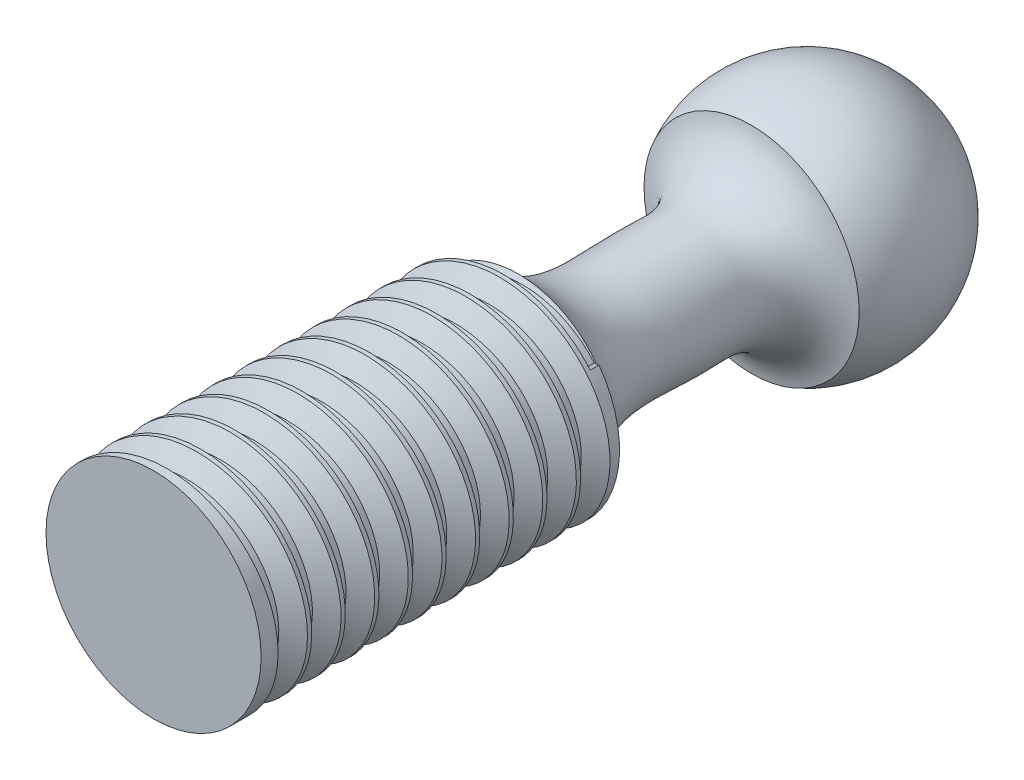
SolidWorks part; units mm, degrees
material "AISI 316L"
ref_plane "Piano frontale" through (0, 0, 0) normal (0, 0, 1) x (1, 0, 0)
ref_plane "Piano superiore" through (0, 0, 0) normal (0, 1, 0) x (1, 0, 0)
ref_plane "Piano destro" through (0, 0, 0) normal (1, 0, 0) x (0, 0, -1)
sketch "Schizzo2" plane through (0, 0, 0) normal (0, 0, 1) x (1, 0, 0)
  line L0 (13.398, -1.3546) -> (22.398, -1.3546)
  arc A0 (22.398, -1.3546) -> (13.398, -1.3546) centre (17.898, -1.3546) ccw
  dimension "D1" = 9
revolve "Rivoluzione1" add sketch "Schizzo2" angle 360 about L0
sketch "Schizzo3" plane through (0, 0, 0) normal (0, 0, 1) x (1, 0, 0)
  circle A0 centre (17.898, -1.3546) radius 4
  dimension "D1" = 8
extrude "Estrusione-Estrusione1" add sketch "Schizzo3" along normal blind 24.3
thread "Filettatura1" pitch 1.25 method cut profile "Profilo filettatura1" start angle 360, offset 0, length 13, pitch 1.25, diameter 8
ref_plane "Piano1" through (13.898, -1.3546, 24.3) normal (0, -1, 0) x (-1, 0, 0)
sketch "Profilo filettatura1" plane through (13.898, -1.3546, 24.3) normal (0, -1, 0) x (-1, 0, 0)
  line L0 (0, 0) -> (0, 1.25) construction
  line L11 (0, 0) -> (0, 1.0937)
  line L12 (0, 1.0937) -> (-0.6766, 0.7031)
  line L13 (-0.6766, 0.7031) -> (-0.6766, 0.3906)
  line L15 (-0.6766, 0.3906) -> (0, 0)
  line L17 (-0.6766, 0.5469) -> (0, 0.5469) construction
  point P2 (0, 0)
  dimension "Pitch" = 1.25
  dimension "Profile_Angle" = 60
  dimension "Profile_Land" = 0.3125
  dimension "Profile_Height" = 0.6766
sketch "Schizzo4" plane through (0, 0, 0) normal (0, 1, 0) x (1, 0, 0)
  line L0 (13.898, -2.0616) -> (21.898, -2.0616) construction
  line L1 (21.898, -11.3313) -> (21.898, -2.0616) construction
  line L2 (21.898, -2.0616) -> (21.898, -10.1117)
  line L3 (17.898, -2.0616) -> (17.898, -10.3938) construction
  arc A0 (21.898, -2.0616) -> (21.898, -10.1117) centre (26.3476, -6.0866) ccw
  spline S0 degree 2 poles (13.898, -23.2063) (13.898, -23.1281) (15.0696, -23.05) (16.2411, -22.9719) (17.898, -22.8937) (19.5549, -22.8156) (20.7264, -22.7375) (21.898, -22.6594) (21.898, -22.5812) (21.898, -22.5031) (20.7264, -22.425) (19.5549, -22.3469) (17.898, -22.2687) (16.2411, -22.1906) (15.0696, -22.1125) (13.898, -22.0344) (13.898, -21.9563) (13.898, -21.8781) (15.0696, -21.8) (16.2411, -21.7219) (17.898, -21.6437) (19.5549, -21.5656) (20.7264, -21.4875) (21.898, -21.4094) (21.898, -21.3312) (21.898, -21.2531) (20.7264, -21.175) (19.5549, -21.0969) (17.898, -21.0187) (16.2411, -20.9406) (15.0696, -20.8625) (13.898, -20.7844) (13.898, -20.7063) (13.898, -20.6281) (15.0696, -20.55) (16.2411, -20.4719) (17.898, -20.3937) (19.5549, -20.3156) (20.7264, -20.2375) (21.898, -20.1594) (21.898, -20.0812) (21.898, -20.0031) (20.7264, -19.925) (19.5549, -19.8469) (17.898, -19.7687) (16.2411, -19.6906) (15.0696, -19.6125) (13.898, -19.5344) (13.898, -19.4563) (13.898, -19.3781) (15.0696, -19.3) (16.2411, -19.2219) (17.898, -19.1437) (19.5549, -19.0656) (20.7264, -18.9875) (21.898, -18.9094) (21.898, -18.8312) (21.898, -18.7531) (20.7264, -18.675) (19.5549, -18.5969) (17.898, -18.5187) (16.2411, -18.4406) (15.0696, -18.3625) (13.898, -18.2844) (13.898, -18.2063) (13.898, -18.1281) (15.0696, -18.05) (16.2411, -17.9719) (17.898, -17.8937) (19.5549, -17.8156) (20.7264, -17.7375) (21.898, -17.6594) (21.898, -17.5812) (21.898, -17.5031) (20.7264, -17.425) (19.5549, -17.3469) (17.898, -17.2688) (16.2411, -17.1906) (15.0696, -17.1125) (13.898, -17.0344) (13.898, -16.9563) (13.898, -16.8781) (15.0696, -16.8) (16.2411, -16.7219) (17.898, -16.6438) (19.5549, -16.5656) (20.7264, -16.4875) (21.898, -16.4094) (21.898, -16.3312) (21.898, -16.2531) (20.7264, -16.175) (19.5549, -16.0969) (17.898, -16.0188) (16.2411, -15.9406) (15.0696, -15.8625) (13.898, -15.7844) (13.898, -15.7063) (13.898, -15.6281) (15.0696, -15.55) (16.2411, -15.4719) (17.898, -15.3938) (19.5549, -15.3156) (20.7264, -15.2375) (21.898, -15.1594) (21.898, -15.0812) (21.898, -15.0031) (20.7264, -14.925) (19.5549, -14.8469) (17.898, -14.7688) (16.2411, -14.6906) (15.0696, -14.6125) (13.898, -14.5344) (13.898, -14.4563) (13.898, -14.3781) (15.0696, -14.3) (16.2411, -14.2219) (17.898, -14.1438) (19.5548, -14.0656) (20.7264, -13.9875) (21.898, -13.9094) (21.898, -13.8312) (21.898, -13.7531) (20.7264, -13.675) (19.5548, -13.5969) (17.898, -13.5188) (16.2411, -13.4406) (15.0696, -13.3625) (13.898, -13.2844) (13.898, -13.2063) (13.898, -13.1281) (15.0696, -13.05) (16.2411, -12.9719) (17.898, -12.8938) (19.5548, -12.8156) (20.7264, -12.7375) (21.898, -12.6594) (21.898, -12.5812) (21.898, -12.5031) (20.7264, -12.425) (19.5548, -12.3469) (17.898, -12.2688) (16.2411, -12.1906) (15.0696, -12.1125) (13.898, -12.0344) (13.898, -11.9563) (13.898, -11.8781) (15.0696, -11.8) (16.2411, -11.7219) (17.898, -11.6438) (19.5548, -11.5656) (20.7264, -11.4875) (21.898, -11.4094) (21.898, -11.3312) (21.898, -11.2531) (20.7264, -11.175) (19.5548, -11.0969) (17.898, -11.0188) (16.2411, -10.9406) (15.0696, -10.8625) (13.898, -10.7844) (13.898, -10.7063) (13.898, -10.6281) (15.0696, -10.55) (16.2411, -10.4719) (17.898, -10.3938) (19.5548, -10.3156) (20.7264, -10.2375) (20.949, -10.2227) (21.1341, -10.207) knots 0 0 0 0.011364 0.011364 0.022727 0.022727 0.034091 0.034091 0.045455 0.045455 0.056818 0.056818 0.068182 0.068182 0.079545 0.079545 0.090909 0.090909 0.102273 0.102273 0.113636 0.113636 0.125 0.125 0.136364 0.136364 0.147727 0.147727 0.159091 0.159091 0.170455 0.170455 0.181818 0.181818 0.193182 0.193182 0.204545 0.204545 0.215909 0.215909 0.227273 0.227273 0.238636 0.238636 0.25 0.25 0.261364 0.261364 0.272727 0.272727 0.284091 0.284091 0.295455 0.295455 0.306818 0.306818 0.318182 0.318182 0.329545 0.329545 0.340909 0.340909 0.352273 0.352273 0.363636 0.363636 0.375 0.375 0.386364 0.386364 0.397727 0.397727 0.409091 0.409091 0.420455 0.420455 0.431818 0.431818 0.443182 0.443182 0.454545 0.454545 0.465909 0.465909 0.477273 0.477273 0.488636 0.488636 0.5 0.5 0.511364 0.511364 0.522727 0.522727 0.534091 0.534091 0.545455 0.545455 0.556818 0.556818 0.568182 0.568182 0.579545 0.579545 0.590909 0.590909 0.602273 0.602273 0.613636 0.613636 0.625 0.625 0.636364 0.636364 0.647727 0.647727 0.659091 0.659091 0.670455 0.670455 0.681818 0.681818 0.693182 0.693182 0.704545 0.704545 0.715909 0.715909 0.727273 0.727273 0.738636 0.738636 0.75 0.75 0.761364 0.761364 0.772727 0.772727 0.784091 0.784091 0.795455 0.795455 0.806818 0.806818 0.818182 0.818182 0.829545 0.829545 0.840909 0.840909 0.852273 0.852273 0.863636 0.863636 0.875 0.875 0.886364 0.886364 0.897727 0.897727 0.909091 0.909091 0.920455 0.920455 0.931818 0.931818 0.943182 0.943182 0.945483 0.945483 0.945483 weights 1 0.92388 1 0.92388 1 0.92388 1 0.92388 1 0.92388 1 0.92388 1 0.92388 1 0.92388 1 0.92388 1 0.92388 1 0.92388 1 0.92388 1 0.92388 1 0.92388 1 0.92388 1 0.92388 1 0.92388 1 0.92388 1 0.92388 1 0.92388 1 0.92388 1 0.92388 1 0.92388 1 0.92388 1 0.92388 1 0.92388 1 0.92388 1 0.92388 1 0.92388 1 0.92388 1 0.92388 1 0.92388 1 0.92388 1 0.92388 1 0.92388 1 0.92388 1 0.92388 1 0.92388 1 0.92388 1 0.92388 1 0.92388 1 0.92388 1 0.92388 1 0.92388 1 0.92388 1 0.92388 1 0.92388 1 0.92388 1 0.92388 1 0.92388 1 0.92388 1 0.92388 1 0.92388 1 0.92388 1 0.92388 1 0.92388 1 0.92388 1 0.92388 1 0.92388 1 0.92388 1 0.92388 1 0.92388 1 0.92388 1 0.92388 1 0.92388 1 0.92388 1 0.92388 1 0.92388 1 0.92388 1 0.92388 1 0.92388 1 0.92388 1 0.92388 1 0.92388 1 0.92388 1 0.92388 1 0.92388 1 0.92388 1 0.92388 1 0.92388 1 0.92388 1 0.92388 1 0.92388 1 0.984586 0.975414 construction
  dimension "D1" = 6
ref_axis "Assi1" through (17.898, -1.3546, 24.3) along (0, 0, -1)
ref_plane "Piano2" through (17.898, 0, 0) normal (1, 0, 0) x (0, 0, -1)
sketch "Schizzo5" plane through (17.898, 0, 0) normal (1, 0, 0) x (0, 0, -1)
  line L0 (-11.0188, -5.3546) -> (-2.0616, -5.3546) construction
  line L1 (-10.9721, -5.3546) -> (-2.0616, -5.3546)
  spline S0 degree 3 poles (-10.9721, -5.3546) (-10.5781, -4.4406) (-9.3242, -3.6354) (-7.1738, -3.4303) (-5.5202, -3.5879) (-3.3905, -3.3886) (-2.2231, -4.4565) (-2.0616, -5.3546) knots 0 0 0 0 0.270255 0.398618 0.616505 0.750648 1 1 1 1
revolve "Taglia-Rivoluzione2" cut sketch "Schizzo5" angle 360 about axis through (17.898, -1.3546, 24.3) along (0, 0, -1)
